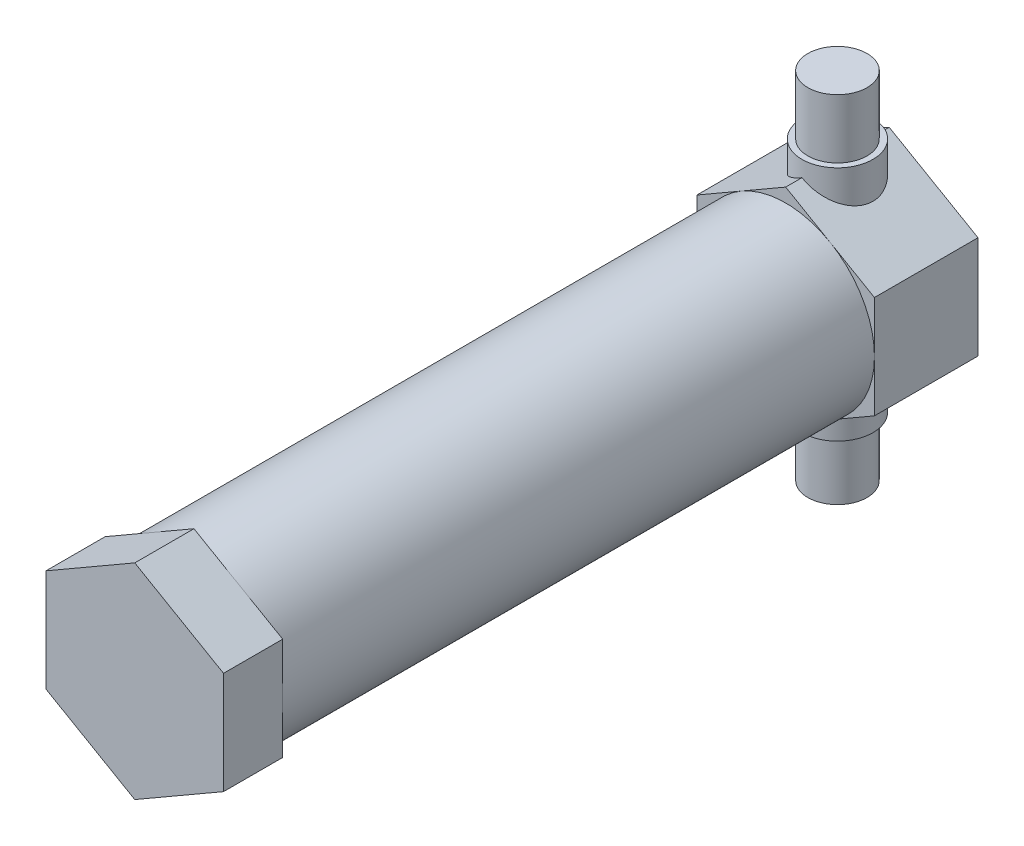
SolidWorks part; units mm, degrees
ref_plane "Front Plane" through (0, 0, 0) normal (0, 0, 1) x (1, 0, 0)
ref_plane "Top Plane" through (0, 0, 0) normal (0, 1, 0) x (1, 0, 0)
ref_plane "Right Plane" through (0, 0, 0) normal (1, 0, 0) x (0, 0, -1)
sketch "Sketch6" plane through (0, 0, 0) normal (0, 0, 1) x (1, 0, 0)
  circle A0 centre (0, 0) radius 9.525
  dimension "D1" = 19.05
extrude "Boss-Extrude5" add sketch "Sketch6" along normal blind 80.9625
sketch "Sketch7" plane through (0, 0, 80.9625) normal (0, 0, 1) x (1, 0, 0)
  line L1 (0, 10.9985) -> (-9.525, 5.4993)
  line L2 (-9.525, 5.4993) -> (-9.525, -5.4993)
  line L3 (-9.525, -5.4993) -> (0, -10.9985)
  line L4 (0, -10.9985) -> (9.525, -5.4993)
  line L5 (9.525, -5.4993) -> (9.525, 5.4993)
  line L6 (9.525, 5.4993) -> (0, 10.9985)
  circle A0 centre (0, 0) radius 9.525 construction
  circle A1 centre (0, 0) radius 9.525 construction
extrude "Boss-Extrude6" add sketch "Sketch7" against normal blind 6.35 contours L6 L1 L2 L3 L4 L5
sketch "Sketch8" plane through (0, 0, 0) normal (0, 0, -1) x (-1, 0, 0)
  line L0 (0, 10.9985) -> (4.7625, 8.2489) construction
  line L1 (0, 10.9985) -> (-9.525, 5.4993)
  line L2 (-9.525, 5.4993) -> (-9.525, -5.4993)
  line L3 (-9.525, -5.4993) -> (0, -10.9985)
  line L4 (0, -10.9985) -> (9.525, -5.4993)
  line L5 (9.525, -5.4993) -> (9.525, 5.4993)
  line L6 (9.525, 5.4993) -> (0, 10.9985)
  circle A0 centre (0, 0) radius 9.525 construction
extrude "Boss-Extrude7" add sketch "Sketch8" against normal blind 11.1125 contours L1 L2 L3 L4 L5 L6
sketch "Sketch9" plane through (0, 0, 0) normal (0, 1, 0) x (1, 0, 0)
  line L0 (0, -11.1125) -> (0, 0) construction
  circle A0 centre (0, -5.5562) radius 3.175
  dimension "D1" = 6.35
extrude "Boss-Extrude8" add sketch "Sketch9" along normal mid plane 38.1
sketch "Sketch11" plane through (0, 0, 0) normal (0, 1, 0) x (1, 0, 0)
  circle A0 centre (0, -5.5562) radius 3.81
  dimension "D1" = 7.62
extrude "Boss-Extrude9" add sketch "Sketch11" along normal mid plane 25.4
sketch "Sketch12" plane through (0, 0, 0) normal (0, 0, -1) x (-1, 0, 0)
  circle A0 centre (0, 0) radius 6.35
  dimension "D1" = 12.7
extrude "Cut-Extrude2" cut sketch "Sketch12" against normal blind 50.8
